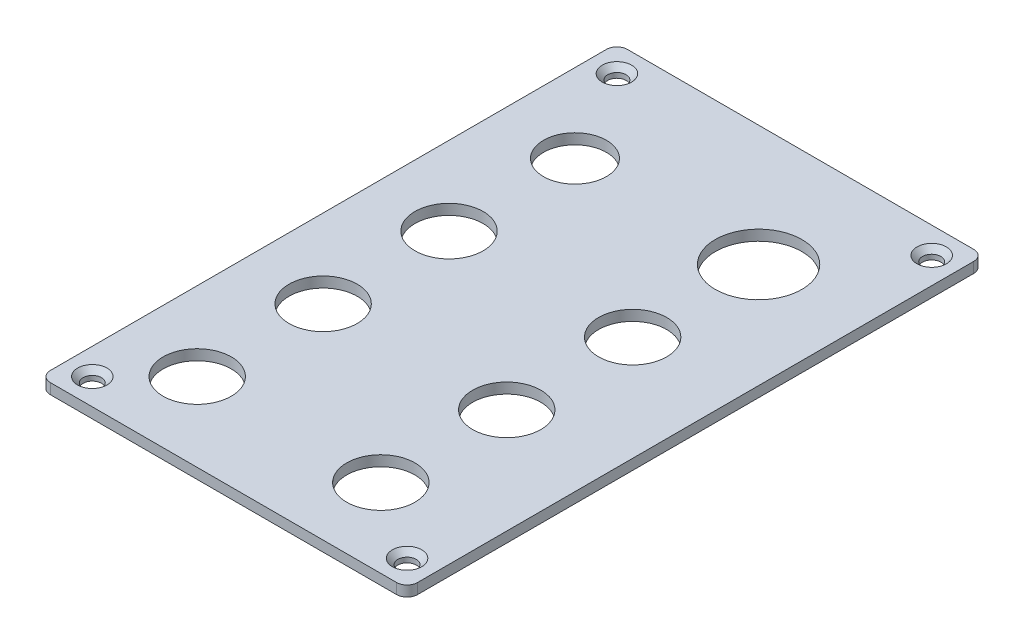
SolidWorks part; units mm, degrees
ref_plane "Front Plane" through (0, 0, 0) normal (0, 0, 1) x (1, 0, 0)
ref_plane "Top Plane" through (0, 0, 0) normal (0, 1, 0) x (1, 0, 0)
ref_plane "Right Plane" through (0, 0, 0) normal (1, 0, 0) x (0, 0, -1)
sketch "Face Plate" plane through (0, 0, 0) normal (0, 1, 0) x (1, 0, 0)
  line L1 (35, -55) -> (-35, -55)
  line L2 (35, -55) -> (35, 55)
  line L3 (35, 55) -> (-35, 55)
  line L4 (-35, -55) -> (-35, 55)
  line L5 (35, -55) -> (-35, 55) construction
  line L6 (35, 55) -> (-35, -55) construction
  point P0 (0, 0)
  dimension "D1" = 70
  dimension "D2" = 110
extrude "Face Plate Ext" add sketch "Face Plate" along normal blind 2
sketch "Buttons" plane through (0, 2, 0) normal (0, 1, 0) x (1, 0, 0)
  line L0 (35, -55) -> (35, 55) construction
  line L1 (-35, -55) -> (35, -55) construction
  line L5 (-35, 55) -> (-35, -55) construction
  line L6 (35, 55) -> (-35, 55) construction
  line L8 (-20, 32) -> (-20, -40) construction
  line L10 (0, 0) -> (0, 17.9718) construction
  circle A0 centre (-20, 32) radius 6
  circle A1 centre (15, 32) radius 8.25
  circle A2 centre (-20, 8) radius 6.5
  circle A3 centre (15, 8) radius 6.5
  circle A4 centre (-20, -16) radius 6.5
  circle A5 centre (-20, -40) radius 6.5
  circle A6 centre (15, -16) radius 6.5
  circle A7 centre (15, -40) radius 6.5
  dimension "D6" = 23
  dimension "D7" = 12
  dimension "D5" = 15
  dimension "D9" = 16.5
  dimension "D2" = 20
  dimension "D3" = 13
  dimension "D4" = 15
  dimension "D11" = 24
  dimension "D13" = 13
  dimension "D14" = 13
  dimension "D8" = 24
  dimension "D12" = 24
  dimension "BTN_DISTANCE" = 72
extrude "Buttons CUT" cut sketch "Buttons" against normal blind 10
sketch "M3 Top Screw" plane through (0, 2, 0) normal (0, 1, 0) x (1, 0, 0)
  line L0 (-35, 55) -> (-35, -55) construction
  line L1 (35, 55) -> (-35, 55) construction
  line L2 (35, -55) -> (35, 55) construction
  line L3 (-35, -55) -> (35, -55) construction
  circle A0 centre (-30, 50) radius 1.75
  circle A1 centre (30, 50) radius 1.75
  circle A2 centre (-30, -50) radius 1.75
  circle A3 centre (30, -50) radius 1.75
  dimension "D1" = 3.5
  dimension "D2" = 5
  dimension "D3" = 5
  dimension "D4" = 5
  dimension "D5" = 5
extrude "M3 Top Screw CUT" cut sketch "M3 Top Screw" against normal blind 10
sketch "M3 Head Top" plane through (0, 2, 0) normal (0, 1, 0) x (1, 0, 0)
  circle A0 centre (-30, 50) radius 2.8
  circle A1 centre (30, 50) radius 2.8
  circle A2 centre (30, -50) radius 2.8
  circle A3 centre (-30, -50) radius 2.8
  dimension "D1" = 5.6
extrude "M3 Head Top CUT" cut sketch "M3 Head Top" against normal blind 10 draft 45
fillet "Fillet1" radius 2 1 edges at (-35, 1, -55) type face fillet first side face at (-35, 1, 0) second side face at (0, 1, -55)
fillet "Fillet2" radius 2 1 edges at (35, 1, -55) type face fillet first side face at (1, 1, -55) second side face at (35, 1, 0)
fillet "Fillet3" radius 2 1 edges at (35, 1, 55) type face fillet first side face at (35, 1, 1) second side face at (0, 1, 55)
fillet "Fillet4" radius 2 1 edges at (-35, 1, 55) type face fillet first side face at (-1, 1, 55) second side face at (-35, 1, 1)
equation "\"BUTTON_PUSH\"= 13mm"
equation "\"BUTTON_METAL\"= 16.5mm"
equation "\"BUTTON_TOGGLE\"= 12mm"
equation "\"SPACER_LEFT\"= 15"
equation "\"ENCODER\"=7.1"
equation "\"SCREW_M3\"=3.5"
equation "\"D1@M3 Top Screw\"=\"SCREW_M3\""
equation "\"SPACER_COVER_SCREW\"=5"
equation "\"D2@M3 Top Screw\"=\"SPACER_COVER_SCREW\""
equation "\"D3@M3 Top Screw\"=\"SPACER_COVER_SCREW\""
equation "\"D4@M3 Top Screw\"=\"SPACER_COVER_SCREW\""
equation "\"D5@M3 Top Screw\"=\"SPACER_COVER_SCREW\""
equation "\"SCREW_M3_HEAD\"=5.6"
equation "\"D1@M3 Head Top\"=\"SCREW_M3_HEAD\""
equation "\"D5@Buttons\" = \"SPACER_LEFT\""
equation "\"SPACER_TOP\"= 23mm"
equation "\"D6@Buttons\"=\"SPACER_TOP\""
equation "\"SPACER_RIGHT\"= 20mm"
equation "\"D2@Buttons\"=\"SPACER_RIGHT\""
equation "\"SPACER_BOTTOM\"= 15mm"
equation "\"D4@Buttons\"=\"SPACER_BOTTOM\""
equation "\"D7@Buttons\"=\"BUTTON_TOGGLE\""
equation "\"D9@Buttons\"=\"BUTTON_METAL\""
equation "\"D3@Buttons\"=\"BUTTON_PUSH\""
equation "\"D13@Buttons\"=\"BUTTON_PUSH\""
equation "\"D14@Buttons\"=\"BUTTON_PUSH\""
equation "\"SPACER_THIRD\"= \"BTN_DISTANCE@Buttons\" / 3"
equation "\"SPACER_FOURTH\"= \"BTN_DISTANCE@Buttons\" / 4"
equation "\"D8@Buttons\"=\"SPACER_THIRD\""
equation "\"D11@Buttons\"=\"SPACER_THIRD\""
equation "\"D12@Buttons\"=\"SPACER_THIRD\""
